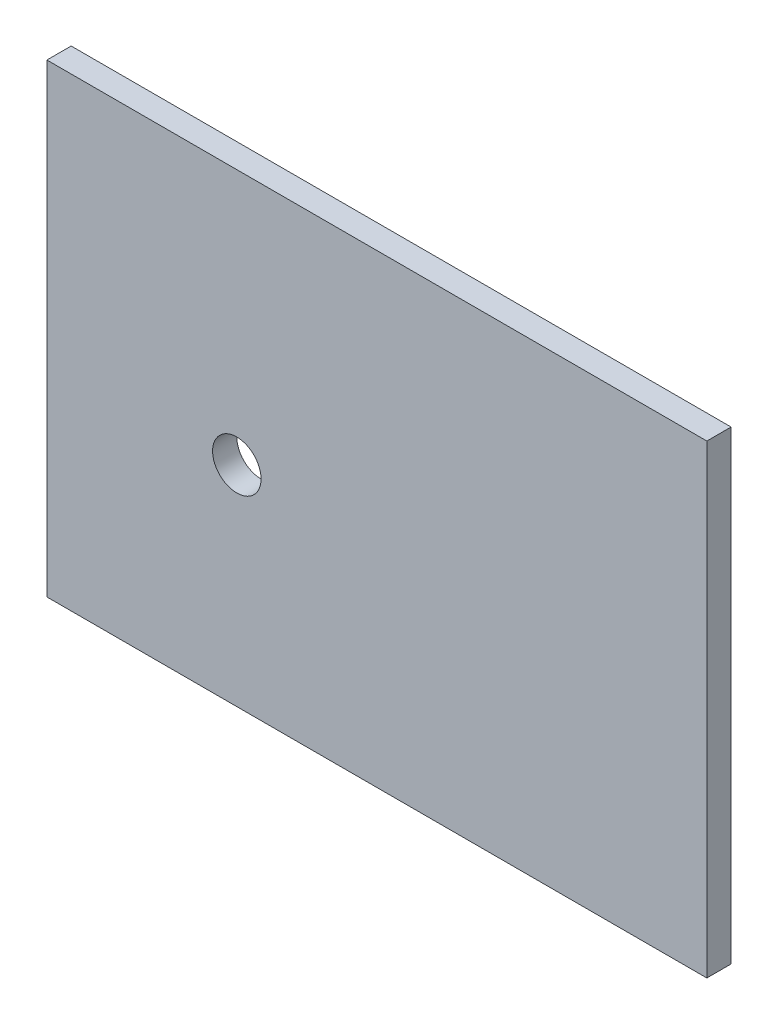
SolidWorks part; units mm, degrees
ref_plane "Plano frontal" through (0, 0, 0) normal (0, 0, 1) x (1, 0, 0)
ref_plane "Plano superior" through (0, 0, 0) normal (0, 1, 0) x (1, 0, 0)
ref_plane "Plano direito" through (0, 0, 0) normal (1, 0, 0) x (0, 0, -1)
sketch "Esboço1" plane through (0, 0, 0) normal (0, 0, 1) x (1, 0, 0)
  line L0 (-31.3285, 42.1937) -> (-31.3285, -34.5221)
  line L1 (-31.3285, 42.1937) -> (77.5348, 42.1937)
  line L2 (77.5348, -34.5221) -> (-31.3285, -34.5221)
  line L3 (-31.3285, -34.5221) -> (-30.9632, -33.4261)
  line L4 (77.5348, 42.1937) -> (77.5348, -34.5221)
  circle A0 centre (0, 0) radius 4
extrude "Ressalto-extrusão1" add sketch "Esboço1" along normal blind 4 contours L0 L1 L4 L2 | A0
